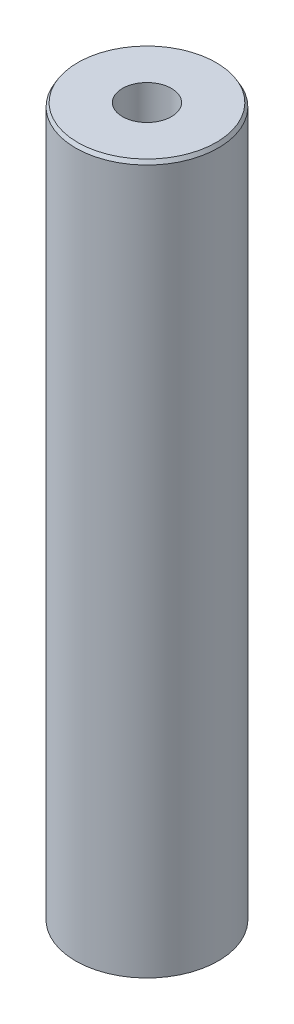
SolidWorks part; units mm, degrees
ref_plane "Front Plane" through (0, 0, 0) normal (0, 0, 1) x (1, 0, 0)
ref_plane "Top Plane" through (0, 0, 0) normal (0, 1, 0) x (1, 0, 0)
ref_plane "Right Plane" through (0, 0, 0) normal (1, 0, 0) x (0, 0, -1)
sketch "Sketch1" plane through (0, 0, 0) normal (0, 1, 0) x (1, 0, 0)
  circle A0 centre (0, 0) radius 10
  dimension "SHAFT_OD" = 20
extrude "Boss-Extrude1" add sketch "Sketch1" along normal blind 99.4656
sketch "Sketch2" plane through (0, 0, 0) normal (0, 1, 0) x (1, 0, 0)
  circle A0 centre (0, 0) radius 3.4329
  dimension "BORE_D" = 6.8658
extrude "Cut-Extrude1" cut sketch "Sketch2" along normal through all
chamfer "Chamfer1" distance 0.5191 angle 30 2 edges at (0, 99.4656, 10) (0, 0, 10) first distance on face at (0, 99.4656, 10) first distance on face at (0, 0, 3.4329)
